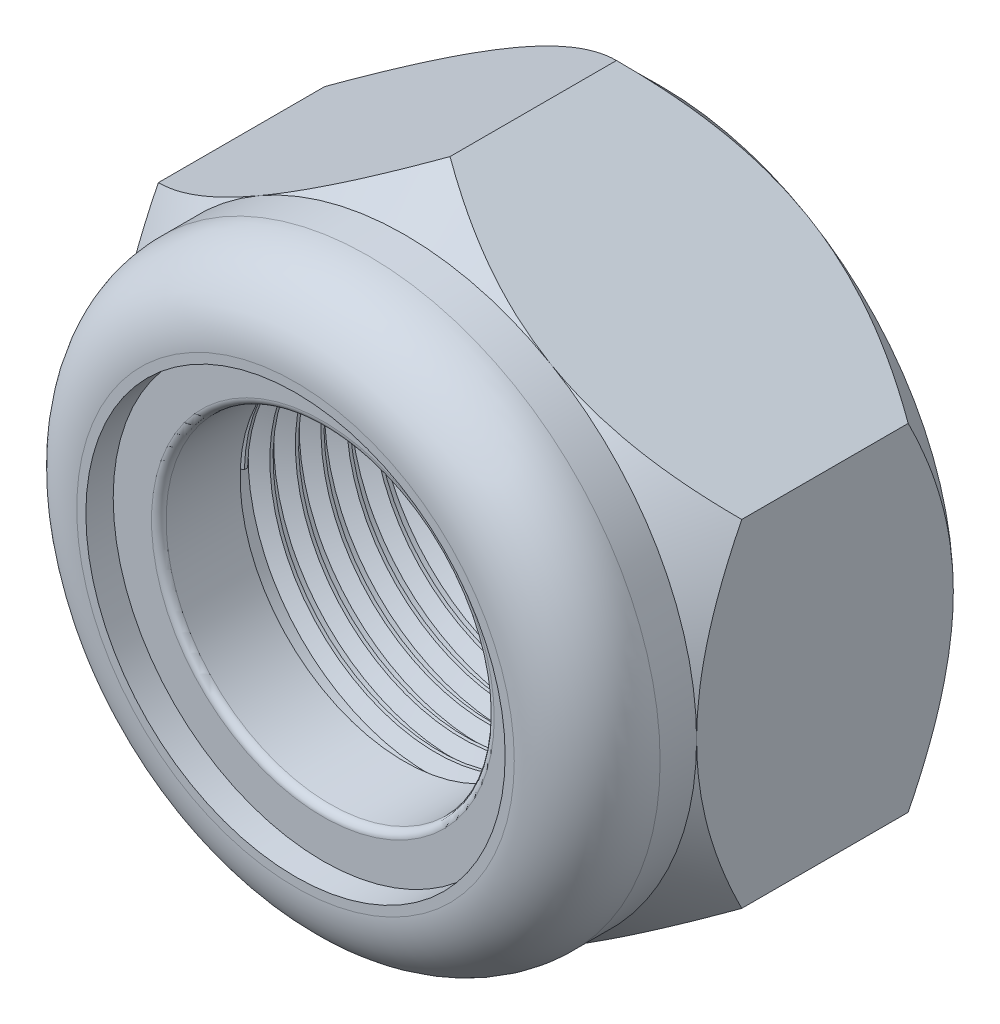
SolidWorks part; units mm, degrees
material "AISI 316 Stainless Steel Sheet (SS)"
ref_plane "Front Plane" through (0, 0, 0) normal (0, 0, 1) x (1, 0, 0)
ref_plane "Top Plane" through (0, 0, 0) normal (0, 1, 0) x (1, 0, 0)
ref_plane "Right Plane" through (0, 0, 0) normal (1, 0, 0) x (0, 0, -1)
sketch "Sketch1" plane through (0, 0, 0) normal (0, 0, 1) x (1, 0, 0)
  line L1 (0, -4.6188) -> (4, -2.3094)
  line L2 (4, -2.3094) -> (4, 2.3094)
  line L3 (4, 2.3094) -> (0, 4.6188)
  line L4 (0, 4.6188) -> (-4, 2.3094)
  line L5 (-4, 2.3094) -> (-4, -2.3094)
  line L6 (-4, -2.3094) -> (0, -4.6188)
  circle A0 centre (0, 0) radius 4 construction
  circle A1 centre (0, 0) radius 2.5
  dimension "D1" = 8
  dimension "D2" = 5
extrude "Boss-Extrude1" add sketch "Sketch1" along normal mid plane 3.52
sketch "Sketch3" plane through (0, 0, 1.76) normal (0, 0, 1) x (1, 0, 0)
  circle A0 centre (0, 0) radius 4
extrude "Cut-Extrude4" cut sketch "Sketch3" against normal blind 3.52 draft 45 flip side to cut
mirror "Mirror1" about plane through (0, 0, 0) normal (0, 0, 1) of "Cut-Extrude4"
sketch "Sketch4" plane through (0, 0, 1.76) normal (0, 0, 1) x (1, 0, 0)
  circle A0 centre (0, 0) radius 2.875
  arc A6 (2, -3.4641) -> (4, 0) centre (0, 0) ccw
  arc A7 (4, 0) -> (2, 3.4641) centre (0, 0) ccw
  arc A8 (2, 3.4641) -> (-2, 3.4641) centre (0, 0) ccw
  arc A9 (-2, 3.4641) -> (-4, 0) centre (0, 0) ccw
  arc A10 (-4, 0) -> (-2, -3.4641) centre (0, 0) ccw
  arc A11 (-2, -3.4641) -> (2, -3.4641) centre (0, 0) ccw
  arc A12 (2, -3.4641) -> (4, 0) centre (0, 0) ccw
  arc A13 (4, 0) -> (2, 3.4641) centre (0, 0) ccw
  arc A14 (2, 3.4641) -> (-2, 3.4641) centre (0, 0) ccw
  arc A15 (-2, 3.4641) -> (-4, 0) centre (0, 0) ccw
  arc A16 (-4, 0) -> (-2, -3.4641) centre (0, 0) ccw
  arc A17 (-2, -3.4641) -> (2, -3.4641) centre (0, 0) ccw
  dimension "D1" = 0
extrude "Boss-Extrude2" add sketch "Sketch4" along normal blind 1.5 contours A14 A15 A16 A17 A12 A13 | A0
fillet "Fillet1" radius 1 1 edges at (4, 0, 3.26)
thread "Thread1" pitch 0.35 method extrude profile "Thread Profile1" start angle 0, offset 0, length 3.2, pitch 0.35, diameter 5
ref_plane "Plane1" through (-2.5, 0, 1.76) normal (0, -1, 0) x (-1, 0, 0)
sketch "Thread Profile1" plane through (-2.5, 0, 1.76) normal (0, -1, 0) x (-1, 0, 0)
  line L0 (0, 0) -> (0, 0.35) construction
  line L1 (0, 0.2625) -> (-0.1894, 0.1531)
  line L2 (-0.1894, 0.1531) -> (-0.1894, 0.1094)
  line L3 (-0.1894, 0.1094) -> (0, 0)
  line L4 (-0.1894, 0.1313) -> (0, 0.1313) construction
  line L11 (0, 0.2625) -> (0, 0)
  point P6 (0, 0)
  dimension "Pitch" = 0.35
  dimension "Profile_Angle" = 60
  dimension "Profile_Land" = 0.0437
  dimension "Profile_Height" = 0.1894
ref_plane "Plane2" through (0, 0, 2.51) normal (0, 0, 1) x (1, 0, 0)
sketch "Sketch5" plane through (0, 0, 2.51) normal (0, 0, 1) x (1, 0, 0)
  circle A0 centre (0, 0) radius 2.875
  circle A1 centre (0, 0) radius 2.25
  dimension "D1" = 5.75
  dimension "D2" = 4.5
extrude "Boss-Extrude3" add sketch "Sketch5" along normal blind 0.375 and the other way blind 0.74
fillet "Fillet2" radius 0.1 1 edges at (2.25, 0, 2.885)
